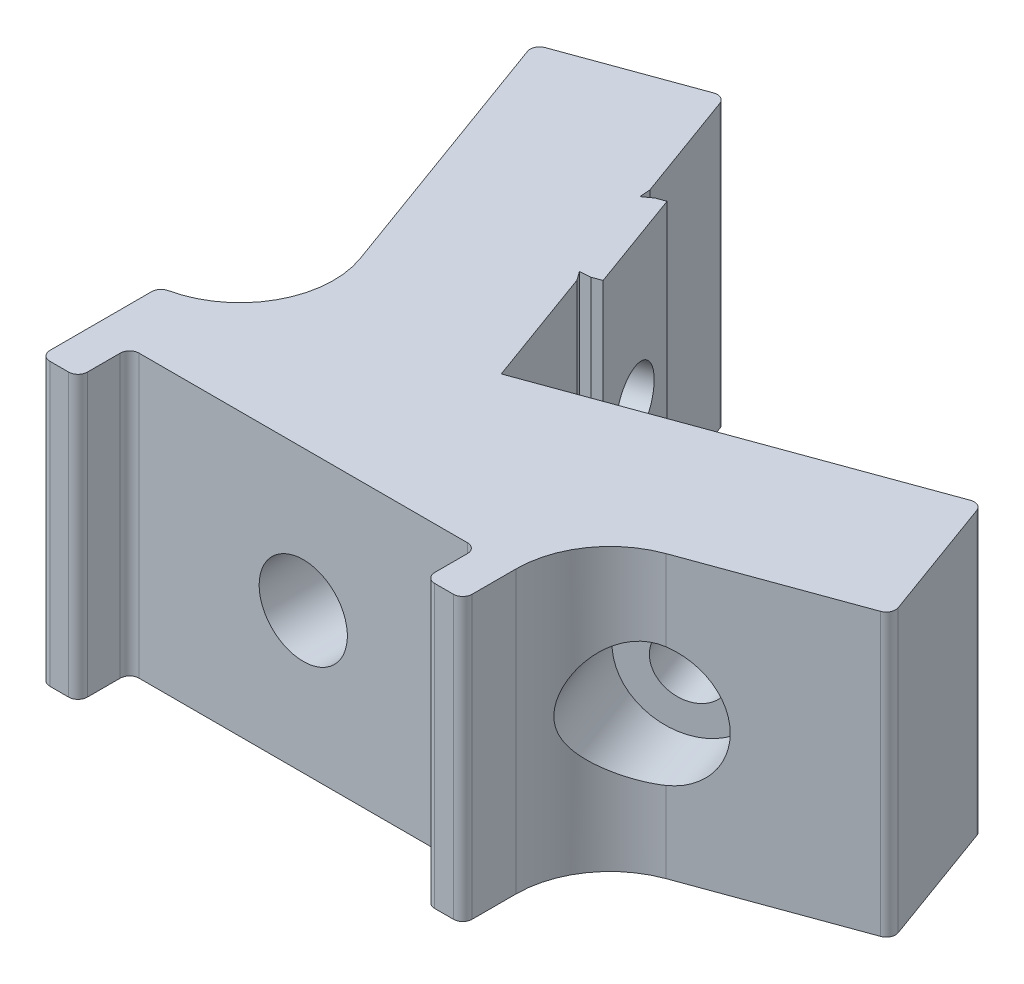
SolidWorks part; units mm, degrees
ref_plane "Front Plane" through (0, 0, 0) normal (0, 0, 1) x (1, 0, 0)
ref_plane "Top Plane" through (0, 0, 0) normal (0, 1, 0) x (1, 0, 0)
ref_plane "Right Plane" through (0, 0, 0) normal (1, 0, 0) x (0, 0, -1)
sketch "Sketch1" plane through (0, 0, 0) normal (0, 1, 0) x (1, 0, 0)
  line L0 (-31.4596, 15.5572) -> (-23.9421, 18.2934)
  line L1 (-23.9421, 18.2934) -> (-17.1017, -0.5005)
  line L2 (-17.1017, -0.5005) -> (1.6922, 6.3399)
  line L3 (1.6922, 6.3399) -> (4.4284, -1.1776)
  line L4 (4.4284, -1.1776) -> (-7.7127, -5.5966)
  line L5 (-7.7127, -5.5966) -> (-23.7602, -5.5966)
  line L6 (-23.7602, -5.5966) -> (-31.4596, 15.5572)
  line L8 (-21.4966, 11.5746) -> (-20.6509, 11.8824)
  line L9 (-20.6509, 11.8824) -> (-18.7014, 6.5261)
  line L10 (-18.7014, 6.5261) -> (-19.5471, 6.2183)
  line L11 (-19.5471, 6.2183) -> (-21.4966, 11.5746)
  line L13 (-18.9627, -5.5966) -> (-23.7602, -5.5966)
  line L17 (-30.2127, -5.5966) -> (-7.7127, -5.5966)
  line L22 (-7.7127, -5.5966) -> (-7.7127, -11.9393)
  line L23 (-7.7127, -11.9393) -> (-9.7127, -11.9393)
  line L24 (-9.7127, -11.9393) -> (-9.7127, -9.1896)
  line L25 (-9.7127, -9.1896) -> (-28.2127, -9.1896)
  line L26 (-28.2127, -9.1896) -> (-28.2127, -11.9393)
  line L27 (-28.2127, -11.9393) -> (-30.2127, -11.9393)
  line L28 (-30.2127, -11.9393) -> (-30.2127, -5.5966)
  line L29 (-19.6761, 9.2043) -> (-20.5219, 8.8964) construction
  point P6 (0, 0)
  dimension "D1" = 90
  dimension "D2" = 0.9
  dimension "D3" = 18.5
  dimension "D4" = 2
  dimension "D5" = 20
  dimension "D6" = 5.7
  dimension "D7" = 8
  dimension "D8" = 2
  dimension "D9" = 20
  dimension "D10" = 8
  dimension "D11" = 110
extrude "Boss-Extrude1" add sketch "Sketch1" along normal blind 15 contours L6 L5 L4 L3 L2 L1 L0 | L10 L9 L8 L1 | L28 L27 L26 L25 L24 L23 L22 L17 L5 | L11 L8 L9 L10 region at (-27.5534, 0, -16.5202) region at (-18.9627, 0, 7.7729) region at (-20.099, 0, -9.0504)
sketch "Sketch2" plane through (0.8965, 0, 2.4631) normal (0.342, 0, 0.9397) x (0.9397, 0, -0.342)
  line L0 (-6.2415, 0) -> (-6.2415, 15) construction
  line L2 (-16.2415, 7.5) -> (3.7585, 7.5) construction
  line L4 (3.7585, 15) -> (3.7585, 0) construction
  circle A1 centre (-6.2415, 7.5) radius 3.25
  point P8 (-6.2415, 7.5)
  dimension "D1" = 20
sketch "Sketch3" plane through (-22.7795, 0, 8.2911) normal (-0.9397, 0, 0.342) x (0.342, 0, 0.9397)
  line L0 (-15.3788, 15) -> (-15.3788, 0) construction
  line L1 (-2.8674, 15) -> (-25.3788, 15) construction
  line L2 (-2.8674, 0) -> (-25.3788, 0) construction
  line L3 (-25.3788, 7.5) -> (-2.8674, 7.5) construction
  line L4 (-25.3788, 15) -> (-25.3788, 0) construction
  line L5 (-2.8674, 15) -> (-2.8674, 0) construction
  line L6 (-18.2288, 15) -> (-12.5288, 15) construction
  line L7 (-18.2288, 0) -> (-12.5288, 0) construction
sketch "Sketch4" plane through (0, 0, 9.1896) normal (0, 0, -1) x (-1, 0, 0)
  line L0 (28.2127, 7.5) -> (9.7127, 7.5) construction
  line L3 (18.9627, 0) -> (18.9627, 15) construction
  line L6 (28.2127, 15) -> (28.2127, 0) construction
  line L7 (9.7127, 15) -> (9.7127, 0) construction
  line L8 (9.7127, 15) -> (28.2127, 15) construction
  line L9 (9.7127, 0) -> (28.2127, 0) construction
  circle A0 centre (18.9627, 7.5) radius 2.35
  point P2 (0, 0)
  point P4 (0, 0)
  point P8 (0, 0)
  point P10 (0, 0)
extrude "Cut-Extrude3" cut sketch "Sketch4" along normal blind 6
hole_wizard "CBORE for M3 Hex Socket Head Cap Screw1" positions "Sketch7" profile "Sketch8" counterbore size "M3" standard "DIN" end condition through all
sketch "Sketch7" plane through (-22.7795, 0, 8.2911) normal (-0.9397, 0, 0.342) x (0.342, 0, 0.9397)
  line L0 (-15.3788, 15) -> (-15.3788, 0) construction
  point P0 (-15.3788, 7.5)
  point P5 (-15.3788, 7.5)
sketch "Sketch8" plane through (-28.0394, 7.5, -6.1603) normal (0, 1, 0) x (0.342, 0, 0.9397)
  line L0 (0, 0) -> (0, 34.6595)
  line L1 (0, 34.6595) -> (1.7, 34.6595)
  line L3 (1.7, 34.6595) -> (1.7, 3.4)
  line L4 (1.7, 3.4) -> (3.25, 3.4)
  line L5 (3.25, 3.4) -> (3.25, 0)
  line L7 (3.25, 0) -> (0, 0)
  line L11 (0, -6.35) -> (0, 107.95) construction
  dimension "Thru Hole Dia." = 3.4
  dimension "Thru Hole Depth" = 34.6595
  dimension "C'Bore Dia." = 6.5
  dimension "C'Bore Depth" = 3.4
hole_wizard "CBORE for M3 Hex Socket Head Cap Screw2" positions "Sketch9" profile "Sketch10" counterbore size "M3" standard "DIN" end condition through all
sketch "Sketch9" plane through (0.8965, 0, 2.4631) normal (0.342, 0, 0.9397) x (0.9397, 0, -0.342)
  line L0 (-6.2415, 0) -> (-6.2415, 15) construction
  point P0 (-6.2415, 7.5)
  point P3 (0, 0)
  point P6 (-6.2415, 7.5)
sketch "Sketch10" plane through (-4.9686, 7.5, 4.5978) normal (0, 1, 0) x (0.9397, 0, -0.342)
  line L0 (0, 0) -> (0, 30.5712)
  line L1 (0, 30.5712) -> (1.7, 30.5712)
  line L3 (1.7, 30.5712) -> (1.7, 3.4)
  line L4 (1.7, 3.4) -> (3.25, 3.4)
  line L5 (3.25, 3.4) -> (3.25, 0)
  line L7 (3.25, 0) -> (0, 0)
  line L11 (0, -6.35) -> (0, 107.95) construction
  dimension "Thru Hole Dia." = 3.4
  dimension "Thru Hole Depth" = 30.5712
  dimension "C'Bore Dia." = 6.5
  dimension "C'Bore Depth" = 3.4
sketch "Sketch11" plane through (0, 15, 0) normal (0, 1, 0) x (1, 0, 0)
  line L0 (-21.6334, 11.9505) -> (-21.5899, 11.3746)
  line L1 (-23.9421, 18.2934) -> (-21.4966, 11.5746) construction
  line L2 (-21.5899, 11.3746) -> (-21.1207, 11.7114)
  line L3 (-21.4966, 11.5746) -> (-20.6509, 11.8824) construction
  line L4 (-21.1207, 11.7114) -> (-21.4966, 11.5746)
  line L5 (-21.4966, 11.5746) -> (-21.6334, 11.9505)
  line L6 (-21.9146, 10.6782) -> (-21.0683, 12.493) construction
  point P11 (0, 0)
  dimension "D1" = 0.4
  dimension "D2" = 45
  dimension "D3" = 0.2
extrude "Cut-Extrude4" cut sketch "Sketch11" against normal through all
ref_plane "Plane1" through (-5.2599, 0, -14.4514) normal (-0.342, 0, -0.9397) x (-0.9397, 0, 0.342)
mirror "Mirror1" about plane through (-5.2599, 0, -14.4514) normal (-0.342, 0, -0.9397) of "Cut-Extrude4"
extrude "Cut-Extrude5" cut sketch "Sketch2" along normal through all
fillet "Fillet4" radius 5 1 edges at (-23.7602, 7.5, 5.5966)
fillet "Fillet5" radius 5 1 edges at (-7.7127, 11.9632, 5.5966)
fillet "Fillet6" radius 0.5 1 edges at (-28.2127, 7.5, 9.1896)
fillet "Fillet7" radius 0.5 1 edges at (-9.7127, 7.5, 9.1896)
fillet "Fillet8" radius 0.5 1 edges at (-28.2127, 7.5, 11.9393)
fillet "Fillet9" radius 0.5 1 edges at (-9.7127, 7.5, 11.9393)
fillet "Fillet10" radius 0.5 1 edges at (-30.2127, 7.5, 11.9393)
fillet "Fillet11" radius 0.5 1 edges at (-7.7127, 7.5, 11.9393)
fillet "Fillet12" radius 0.5 1 edges at (4.4284, 7.5, 1.1776)
fillet "Fillet13" radius 0.5 1 edges at (1.6922, 7.5, -6.3399)
fillet "Fillet14" radius 0.5 1 edges at (-23.9421, 7.5, -18.2934)
fillet "Fillet15" radius 0.5 1 edges at (-31.4596, 7.5, -15.5572)
fillet "Fillet16" radius 0.5 1 edges at (-30.2127, 7.5, 5.5966)
